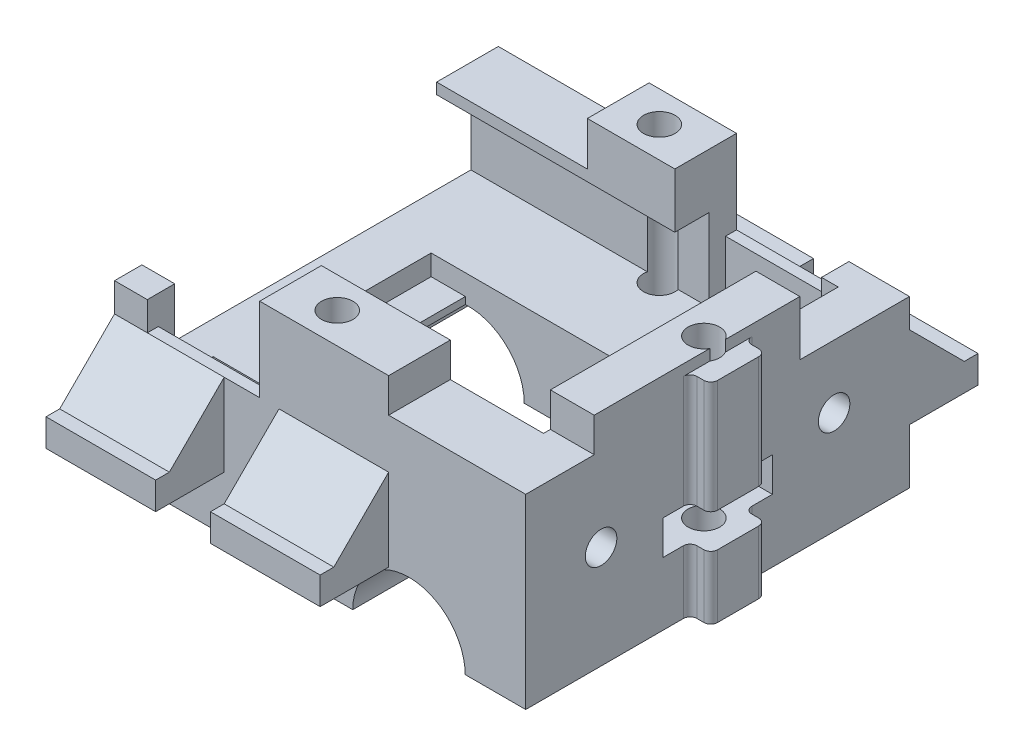
SolidWorks part; units mm, degrees
ref_plane "Front Plane" through (0, 0, 0) normal (0, 0, 1) x (1, 0, 0)
ref_plane "Top Plane" through (0, 0, 0) normal (0, 1, 0) x (1, 0, 0)
ref_plane "Right Plane" through (0, 0, 0) normal (1, 0, 0) x (0, 0, -1)
sketch "Sketch1" plane through (0, 0, 0) normal (1, 0, 0) x (0, 0, -1)
  line L0 (-26.7015, -9.0408) -> (-32.3015, -9.0408) construction
  line L1 (-60.7015, 7.0592) -> (-32.7015, 7.0592)
  line L2 (-60.7015, 7.0592) -> (-60.7015, -9.0408)
  line L3 (-60.7015, -9.0408) -> (-32.7015, -9.0408)
  line L4 (-32.7015, 7.0592) -> (-32.7015, -9.0408)
  dimension "D1" = 16.1
  dimension "D2" = 28
extrude "Boss-Extrude1" add sketch "Sketch1" along normal blind 30
sketch "Sketch2" plane through (0, 0, 60.7015) normal (0, 0, 1) x (1, 0, 0)
  line L7 (30, 7.0592) -> (20, 7.0592)
  line L8 (30, 7.0592) -> (30, 4.5592)
  line L9 (30, 4.5592) -> (20, 4.5592)
  line L10 (20, 7.0592) -> (20, 4.5592)
  dimension "D1" = 10
  dimension "D2" = 2.5
extrude "Cut-Extrude1" cut sketch "Sketch2" against normal blind 5
sketch "Sketch3" plane through (0, 0, 60.7015) normal (0, 0, 1) x (1, 0, 0)
  line L0 (0, 7.0592) -> (0, -9.0408) construction
  line L1 (0, 3.0592) -> (10, 3.0592)
  line L2 (0, 3.0592) -> (0, 7.0592)
  line L3 (0, 7.0592) -> (10, 7.0592)
  line L4 (10, 3.0592) -> (10, 7.0592)
  line L5 (20, 7.0592) -> (0, 7.0592) construction
  dimension "D1" = 4
  dimension "D2" = 10
extrude "Cut-Extrude2" cut sketch "Sketch3" against normal blind 8
sketch "Sketch4" plane through (0, 0, 32.7015) normal (0, 0, -1) x (-1, 0, 0)
  line L6 (-30, 7.0592) -> (0, 7.0592) construction
  line L7 (-1, 7.0592) -> (-11, 7.0592)
  line L8 (-1, 7.0592) -> (-1, 3.8592)
  line L9 (-1, 3.8592) -> (-11, 3.8592)
  line L10 (-11, 7.0592) -> (-11, 3.8592)
  line L11 (0, -9.0408) -> (0, 7.0592) construction
  dimension "D1" = 10
  dimension "D2" = 1
  dimension "D3" = 3.2
extrude "Cut-Extrude3" cut sketch "Sketch4" against normal blind 8
sketch "Sketch5" plane through (0, 0, 32.7015) normal (0, 0, -1) x (-1, 0, 0)
  line L0 (-30, -9.0408) -> (-30, 7.0592) construction
  line L1 (-30, 3.0592) -> (-19, 3.0592)
  line L2 (-30, 3.0592) -> (-30, 7.0592)
  line L3 (-30, 7.0592) -> (-19, 7.0592)
  line L4 (-19, 3.0592) -> (-19, 7.0592)
  line L5 (-30, 7.0592) -> (-11, 7.0592) construction
  dimension "D1" = 4
  dimension "D2" = 11
extrude "Cut-Extrude4" cut sketch "Sketch5" against normal blind 8
sketch "Sketch6" plane through (0, 0, 32.7015) normal (0, 0, -1) x (-1, 0, 0)
  line L0 (-6.4923, -5.0408) -> (-24.9923, -5.0408) construction
  line L1 (-30, -3.0408) -> (-10, -3.0408)
  line L2 (-30, -3.0408) -> (-30, -5.0408)
  line L3 (-30, -5.0408) -> (-10, -5.0408)
  line L4 (-10, -3.0408) -> (-10, -5.0408)
  line L5 (-30, -9.0408) -> (-30, 3.0592) construction
  line L6 (0, -9.0408) -> (0, 7.0592) construction
  dimension "D1" = 0
  dimension "D2" = 10
  dimension "D3" = 2
extrude "Boss-Extrude2" add sketch "Sketch6" along normal blind 5
chamfer "Chamfer1" distance 4 angle 45 1 edges at (20, -3.0408, 32.7015)
sketch "Sketch7" plane through (0, 0, 60.7015) normal (0, 0, 1) x (1, 0, 0)
  line L0 (21.4823, -5.0408) -> (2.9823, -5.0408) construction
  line L1 (0, -3.0408) -> (20, -3.0408)
  line L2 (0, -3.0408) -> (0, -5.0408)
  line L3 (0, -5.0408) -> (20, -5.0408)
  line L4 (20, -3.0408) -> (20, -5.0408)
  line L5 (30, 4.5592) -> (30, -9.0408) construction
  line L6 (0, 3.0592) -> (0, -9.0408) construction
  dimension "D1" = 10
  dimension "D2" = 0
  dimension "D3" = 2
extrude "Boss-Extrude3" add sketch "Sketch7" along normal blind 5
chamfer "Chamfer2" distance 4 angle 45 1 edges at (10, -3.0408, 60.7015)
sketch "Sketch9" plane through (0, 7.0592, 0) normal (0, 1, 0) x (1, 0, 0)
  line L0 (1, -40.7015) -> (1, -32.7015) construction
  line L1 (1, -37.2015) -> (26.8, -37.2015)
  line L2 (1, -37.2015) -> (1, -56.2015)
  line L3 (1, -56.2015) -> (26.8, -56.2015)
  line L4 (26.8, -37.2015) -> (26.8, -56.2015)
  line L5 (30, -32.7015) -> (19, -32.7015) construction
  line L6 (20, -60.7015) -> (10, -60.7015) construction
  line L7 (30, -40.7015) -> (30, -55.7015) construction
  dimension "D1" = 4.5
  dimension "D2" = 4.5
  dimension "D3" = 3.2
extrude "Cut-Extrude6" cut sketch "Sketch9" against normal blind 10
sketch "Sketch13" plane through (0, 0, 60.7015) normal (0, 0, 1) x (1, 0, 0)
  circle A0 centre (21.4823, -9.0408) radius 4.1
  dimension "D1" = 8.2
extrude "Cut-Extrude10" cut sketch "Sketch13" against normal blind 27.2
sketch "Sketch14" plane through (0, 0, 32.7015) normal (0, 0, -1) x (-1, 0, 0)
  circle A0 centre (-6.4923, -9.0408) radius 4.1
  dimension "D1" = 8.2
extrude "Cut-Extrude11" cut sketch "Sketch14" against normal blind 27.2
sketch "Sketch15" plane through (0, -9.0408, 0) normal (0, -1, 0) x (1, 0, 0)
  line L0 (10.5923, 59.9015) -> (10.5923, 32.7015) construction
  line L1 (2.3923, 59.9015) -> (10.5923, 59.9015)
  line L2 (2.3923, 59.9015) -> (2.3923, 55.9015)
  line L3 (2.3923, 55.9015) -> (10.5923, 55.9015)
  line L4 (10.5923, 59.9015) -> (10.5923, 55.9015)
  line L5 (25.5823, 60.7015) -> (25.5823, 33.5015) construction
  line L6 (17.3823, 33.5015) -> (25.5823, 33.5015)
  line L7 (17.3823, 33.5015) -> (17.3823, 37.5015)
  line L8 (17.3823, 37.5015) -> (25.5823, 37.5015)
  line L9 (25.5823, 33.5015) -> (25.5823, 37.5015)
  dimension "D1" = 4
  dimension "D2" = 4
extrude "Cut-Extrude12" cut sketch "Sketch15" against normal blind 27.2
sketch "Sketch16" plane through (0, 7.0592, 0) normal (0, 1, 0) x (1, 0, 0)
  line L1 (10.5923, -59.9015) -> (10, -59.9015)
  line L2 (10.5923, -59.9015) -> (10.5923, -60.7015)
  line L3 (10.5923, -60.7015) -> (10, -60.7015)
  line L4 (10, -59.9015) -> (10, -60.7015)
  line L5 (17.3823, -33.5015) -> (19, -33.5015)
  line L6 (17.3823, -33.5015) -> (17.3823, -32.7015)
  line L7 (17.3823, -32.7015) -> (19, -32.7015)
  line L8 (19, -33.5015) -> (19, -32.7015)
extrude "Cut-Extrude13" cut sketch "Sketch16" against normal up to surface (4 mm away) up to face at (25.3456, 3.0592, 36.0265)
sketch "Sketch17" plane through (0, -9.0408, 0) normal (0, -1, 0) x (1, 0, 0)
  line L0 (30, 60.7015) -> (30, 32.7015) construction
  line L1 (30, 48.7015) -> (31.5, 48.7015)
  line L2 (30, 48.7015) -> (30, 44.7015)
  line L3 (30, 44.7015) -> (31.5, 44.7015)
  line L4 (31.5, 48.7015) -> (31.5, 44.7015)
  line L5 (30, 32.7015) -> (10.5923, 32.7015) construction
  line L6 (30, 60.7015) -> (25.5823, 60.7015) construction
  dimension "D1" = 12
  dimension "D2" = 12
  dimension "D3" = 1.5
extrude "Boss-Extrude4" add sketch "Sketch17" against normal up to surface (16.1 mm away) up to face at (28.4, 7.0592, 48.2015)
fillet "Fillet1" radius 0.5 4 edges at (30, -0.9908, 44.7015) (31.5, -0.9908, 44.7015) (31.5, -0.9908, 48.7015) (30, -0.9908, 48.7015)
sketch "Sketch18" plane through (0, -9.0408, 0) normal (0, -1, 0) x (1, 0, 0)
  line L0 (17.3823, 60.7015) -> (0, 60.7015) construction
  line L1 (0, 60.7015) -> (0, 32.7015) construction
  circle A0 centre (13.985, 46.7015) radius 3.5
  dimension "D1" = 14
  dimension "D2" = 13.985
  dimension "D3" = 7
extrude "Cut-Extrude14" cut sketch "Sketch18" against normal up to surface (6.1 mm away) up to face at (13.9582, -2.9408, 46.7015)
sketch "Sketch19" plane through (31.5, 0, 0) normal (1, 0, 0) x (0, 0, -1)
  line L0 (-32.7015, 0.9592) -> (-32.7015, 3.0592) construction
  line L1 (-50.7015, -1.9408) -> (-42.7015, -1.9408)
  line L2 (-50.7015, -1.9408) -> (-50.7015, -2.9408)
  line L3 (-50.7015, -2.9408) -> (-42.7015, -2.9408)
  line L4 (-42.7015, -1.9408) -> (-42.7015, -2.9408)
  line L5 (-40.7015, 7.0592) -> (-44.2015, 7.0592) construction
  dimension "D1" = 8
  dimension "D2" = 10
  dimension "D3" = 1
  dimension "D4" = 10
extrude "Cut-Extrude15" cut sketch "Sketch19" against normal blind 10
sketch "Sketch20" plane through (0, -2.9408, 0) normal (0, 1, 0) x (1, 0, 0)
  line L0 (10.5923, -56.2015) -> (20, -56.2015) construction
  line L1 (24.3, -41.4015) -> (3.8, -41.4015)
  line L2 (24.3, -41.4015) -> (24.3, -52.0015)
  line L3 (24.3, -52.0015) -> (3.8, -52.0015)
  line L4 (3.8, -41.4015) -> (3.8, -52.0015)
  line L5 (26.8, -55.7015) -> (26.8, -40.7015) construction
  line L6 (17.3823, -37.2015) -> (11, -37.2015) construction
  line L7 (1, -52.7015) -> (1, -32.7015) construction
  dimension "D1" = 4.2
  dimension "D2" = 2.5
  dimension "D3" = 4.2
  dimension "D4" = 2.8
extrude "Cut-Extrude16" cut sketch "Sketch20" against normal blind 1.5
sketch "Sketch21" plane through (0, -2.9408, 0) normal (0, 1, 0) x (1, 0, 0)
  line L0 (24.3, -52.0015) -> (24.3, -41.4015) construction
  line L1 (24.3, -50.7015) -> (30, -50.7015)
  line L2 (24.3, -50.7015) -> (24.3, -42.7015)
  line L3 (24.3, -42.7015) -> (30, -42.7015)
  line L4 (30, -50.7015) -> (30, -42.7015)
extrude "Cut-Extrude17" cut sketch "Sketch21" against normal blind 1.5
sketch "Sketch22" plane through (31.5, 0, 0) normal (1, 0, 0) x (0, 0, -1)
  line L0 (-42.7015, -4.4408) -> (-42.7015, -1.9408) construction
  line L1 (-50.7015, -4.4408) -> (-42.7015, -4.4408)
  line L2 (-50.7015, -4.4408) -> (-50.7015, -1.9408)
  line L3 (-50.7015, -1.9408) -> (-42.7015, -1.9408)
  line L4 (-42.7015, -4.4408) -> (-42.7015, -1.9408)
  dimension "D1" = 2.5
extrude "Cut-Extrude18" cut sketch "Sketch22" against normal blind 1.5
sketch "Sketch23" plane through (0, 7.0592, 0) normal (0, 1, 0) x (1, 0, 0)
  circle A0 centre (29, -46.7015) radius 1.15
  circle A1 centre (14, -34.9515) radius 1.15
  circle A2 centre (14, -58.4515) radius 1.15
  dimension "D1" = 2.3
  dimension "D2" = 2.3
  dimension "D3" = 2.3
extrude "Cut-Extrude19" cut sketch "Sketch23" against normal through all
sketch "Sketch24" plane through (0, 3.0592, 0) normal (0, 1, 0) x (1, 0, 0)
  line L1 (25.5823, -33.5015) -> (17.3823, -33.5015)
  line L2 (25.5823, -33.5015) -> (25.5823, -32.7015)
  line L3 (25.5823, -32.7015) -> (17.3823, -32.7015)
  line L4 (17.3823, -33.5015) -> (17.3823, -32.7015)
  line L5 (2.3923, -59.9015) -> (10.5923, -59.9015)
  line L6 (2.3923, -59.9015) -> (2.3923, -60.7015)
  line L7 (2.3923, -60.7015) -> (10.5923, -60.7015)
  line L8 (10.5923, -59.9015) -> (10.5923, -60.7015)
extrude "Cut-Extrude20" cut sketch "Sketch24" against normal blind 2.1
sketch "Sketch25" plane through (31.5, 0, 0) normal (1, 0, 0) x (0, 0, -1)
  line L0 (-49.2015, 7.0592) -> (-55.7015, 7.0592) construction
  line L1 (-50.5182, 7.0592) -> (-42.5886, 7.0592)
  line L2 (-50.5182, 7.0592) -> (-50.5182, 6.2592)
  line L3 (-50.5182, 6.2592) -> (-42.5886, 6.2592)
  line L4 (-42.5886, 7.0592) -> (-42.5886, 6.2592)
  dimension "D1" = 0.8
extrude "Cut-Extrude21" cut sketch "Sketch25" against normal up to surface (1.5 mm away) up to face at (30, -0.7608, 53.1015)
sketch "Sketch26" plane through (0, 0, 65.7015) normal (0, 0, 1) x (1, 0, 0)
  line L0 (0, -5.0408) -> (20, -5.0408) construction
  line L1 (12, -5.0408) -> (8, -5.0408)
  line L2 (12, -5.0408) -> (12, 0.9592)
  line L3 (12, 0.9592) -> (8, 0.9592)
  line L4 (8, -5.0408) -> (8, 0.9592)
  line L5 (2.3923, 0.9592) -> (10.5923, 0.9592) construction
  line L6 (0, -3.0408) -> (0, 0.9592) construction
  line L7 (20, -5.0408) -> (20, 0.9592) construction
  dimension "D1" = 8
  dimension "D2" = 8
extrude "Cut-Extrude22" cut sketch "Sketch26" against normal up to surface (5 mm away) up to face at (17.0124, -1.4158, 60.7015)
sketch "Sketch27" plane through (0, 0, 27.7015) normal (0, 0, -1) x (-1, 0, 0)
  line L0 (-30, -5.0408) -> (-10, -5.0408) construction
  line L1 (-22, -5.0408) -> (-18, -5.0408)
  line L2 (-22, -5.0408) -> (-22, 0.9592)
  line L3 (-22, 0.9592) -> (-18, 0.9592)
  line L4 (-18, -5.0408) -> (-18, 0.9592)
  line L5 (-17.3823, 0.9592) -> (-10, 0.9592) construction
  line L6 (-10, -5.0408) -> (-10, 0.9592) construction
  line L7 (-30, -3.0408) -> (-30, -5.0408) construction
  dimension "D1" = 8
  dimension "D2" = 8
extrude "Cut-Extrude23" cut sketch "Sketch27" against normal up to surface (5 mm away) up to face at (10.8392, -0.3051, 32.7015)
sketch "Sketch28" plane through (30, 0, 0) normal (1, 0, 0) x (0, 0, -1)
  line L0 (-60.7015, 4.5592) -> (-60.7015, -9.0408) construction
  line L1 (-32.7015, 0.9592) -> (-32.7015, 3.0592) construction
  line L2 (-60.7015, -9.0408) -> (-49.2015, -9.0408) construction
  line L3 (-44.2015, -9.0408) -> (-32.7015, -9.0408) construction
  circle A0 centre (-55.2015, -1.5408) radius 1.15
  circle A1 centre (-38.2015, -1.5408) radius 1.15
  dimension "D1" = 2.3
  dimension "D2" = 2.3
  dimension "D3" = 5.5
  dimension "D4" = 5.5
  dimension "D5" = 7.5
  dimension "D6" = 7.5
extrude "Cut-Extrude24" cut sketch "Sketch28" against normal up to surface (3.2 mm away) up to face at (26.8, 1.1425, 47.2015)
sketch "Sketch29" plane through (0, -4.4408, 0) normal (0, 1, 0) x (1, 0, 0)
  line L0 (3.8, -52.0015) -> (24.3, -52.0015) construction
  line L1 (21.8, -52.0015) -> (6.3, -52.0015)
  line L2 (21.8, -52.0015) -> (21.8, -41.4015)
  line L3 (21.8, -41.4015) -> (6.3, -41.4015)
  line L4 (6.3, -52.0015) -> (6.3, -41.4015)
  line L5 (24.3, -41.4015) -> (3.8, -41.4015) construction
  line L6 (3.8, -41.4015) -> (3.8, -52.0015) construction
  line L7 (24.3, -52.0015) -> (24.3, -50.7015) construction
  dimension "D1" = 2.5
  dimension "D2" = 2.5
extrude "Cut-Extrude25" cut sketch "Sketch29" against normal up to surface (4.6 mm away) up to face at (14, -9.0408, 59.6015)
sketch "Sketch30" plane through (0, 0, 0) normal (-1, 0, 0) x (0, 0, 1)
  line L0 (60.7015, -9.0408) -> (32.7015, -9.0408) construction
  line L1 (34.7015, 3.0592) -> (58.7015, 3.0592)
  line L2 (34.7015, 3.0592) -> (34.7015, -2.9408)
  line L3 (34.7015, -2.9408) -> (58.7015, -2.9408)
  line L4 (58.7015, 3.0592) -> (58.7015, -2.9408)
  line L5 (60.7015, 0.9592) -> (60.7015, 7.0592) construction
  line L6 (32.7015, -9.0408) -> (32.7015, 7.0592) construction
  dimension "D1" = 6.1
  dimension "D2" = 2
  dimension "D3" = 2
  dimension "D4" = 6
extrude "Cut-Extrude27" cut sketch "Sketch30" against normal up to surface (26.8 mm away) contours L1 L4 L3 L2 up to face at (26.8, 0.4717, 47.0765)
sketch "Sketch32" plane through (1, 0, 0) normal (1, 0, 0) x (0, 0, -1)
  line L0 (-32.7015, 3.8592) -> (-37.2015, 3.8592)
  line L1 (-37.2015, 3.8592) -> (-37.2015, 3.0592)
  line L2 (-37.2015, 3.0592) -> (-52.7015, 3.0592)
  line L3 (-52.7015, 3.0592) -> (-52.7015, 7.0592)
  line L4 (-52.7015, 7.0592) -> (-32.7015, 7.0592)
  line L5 (-32.7015, 7.0592) -> (-32.7015, 3.8592)
extrude "Cut-Extrude29" cut sketch "Sketch32" against normal up to surface (1 mm away) up to face at (0, -0.8542, 53.1015)
